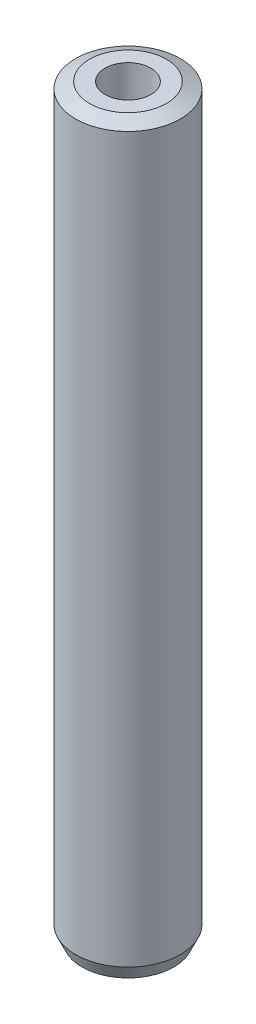
SolidWorks part; units mm, degrees
ref_plane "Front Plane" through (0, 0, 0) normal (0, 0, 1) x (1, 0, 0)
ref_plane "Top Plane" through (0, 0, 0) normal (0, 1, 0) x (1, 0, 0)
ref_plane "Right Plane" through (0, 0, 0) normal (1, 0, 0) x (0, 0, -1)
sketch "Sketch1" plane through (0, 0, 0) normal (0, 1, 0) x (1, 0, 0)
  circle A0 centre (0, 0) radius 40
  dimension "SHAFT_OD" = 80
extrude "Boss-Extrude1" add sketch "Sketch1" along normal blind 568.2729
sketch "Sketch2" plane through (0, 0, 0) normal (0, 1, 0) x (1, 0, 0)
  circle A0 centre (0, 0) radius 17.5089
  dimension "BORE_D" = 35.0179
extrude "Cut-Extrude1" cut sketch "Sketch2" along normal through all
chamfer "Chamfer1" distance 4.8918 angle 65.342 2 edges at (0, 568.2729, 40) (0, 0, 40) first distance on face at (0, 568.2729, 40) first distance on face at (0, 0, 17.5089)
